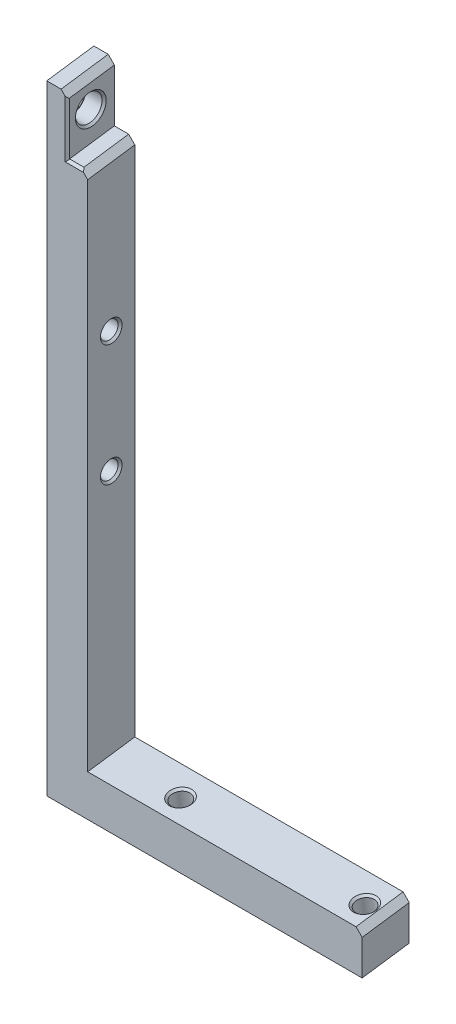
SolidWorks part; units mm, degrees
ref_plane "Top" through (0, 0, 0) normal (0, 0, 1) x (1, 0, 0)
ref_plane "Front" through (0, 0, 0) normal (0, 1, 0) x (1, 0, 0)
ref_plane "Right" through (0, 0, 0) normal (1, 0, 0) x (0, 0, -1)
sketch "Sketch4" plane through (0, 0, 0) normal (1, 0, 0) x (0, 0, -1)
  line L1 (0, 0) -> (11.5, 0)
  line L2 (0, 0) -> (0, 144)
  line L3 (0, 144) -> (11.5, 144)
  line L4 (11.5, 0) -> (11.5, 144)
  dimension "D1" = 11.5
  dimension "D2" = 144
extrude "Boss-Extrude2" add sketch "Sketch4" along normal blind 10
sketch "Sketch6" plane through (10, 0, 0) normal (1, 0, 0) x (0, 0, -1)
  line L0 (5.75, 0) -> (11.5, 0.8081)
  line L1 (0, 0) -> (11.5, 0) construction
  line L2 (11.5, 0) -> (11.5, 144) construction
  line L3 (11.5, 0.8081) -> (10.1083, 10.7108)
  line L4 (10.1083, 10.7108) -> (0.2056, 9.3191)
  line L5 (0.2056, 9.3191) -> (1.5973, -0.5836)
  line L6 (1.5973, -0.5836) -> (5.75, 0)
  line L7 (0, 144) -> (0, 0) construction
  dimension "D1" = 10
  dimension "D2" = 10
  dimension "D3" = 82
extrude "Boss-Extrude3" add sketch "Sketch6" along normal blind 67 and the other way blind 10
sketch "Sketch7" plane through (10, 0, 0) normal (1, 0, 0) x (0, 0, -1)
  line L0 (-3.1126, -1.2456) -> (11.8209, -3.029)
  line L2 (11.8209, -3.029) -> (11.8209, 0.8532)
  line L3 (11.8209, 0.8532) -> (-3.1126, -1.2456)
  line L4 (1.5973, -0.5836) -> (11.5, 0.8081) construction
extrude "Cut-Extrude2" cut sketch "Sketch7" against normal blind 10
sketch "Sketch8" plane through (0, 9.1102, 1.2804) normal (0, 0.9903, 0.1392) x (1, 0, 0)
  line L0 (10, 1.5005) -> (77, 1.5005) construction
  line L1 (77, 11.5005) -> (77, 1.5005) construction
  circle A0 centre (72.5, 6.5005) radius 2.25
  circle A1 centre (27.5, 6.5005) radius 2.25
  dimension "D2" = 4.5
  dimension "D3" = 4.5
  dimension "D1" = 45
  dimension "D4" = 5
  dimension "D5" = 4.5
extrude "Cut-Extrude3" cut sketch "Sketch8" against normal blind 10
sketch "Sketch11" plane through (0, 9.1102, 1.2804) normal (0, 0.9903, 0.1392) x (1, 0, 0)
  line L0 (23.5, 6.5005) -> (23.5, 0)
  line L1 (23.5, 0) -> (31.5, 0)
  line L3 (31.5, 0) -> (31.5, 6.5005)
  line L4 (10, 0) -> (0, 0) construction
  circle A0 centre (27.5, 6.5005) radius 4 construction
  arc A1 (31.5, 6.5005) -> (23.5, 6.5005) centre (27.5, 6.5005) ccw
  dimension "D1" = 8
sketch "Sketch12" plane through (77, 0, 0) normal (1, 0, 0) x (0, 0, -1)
  line L5 (0.2056, 9.3191) -> (10.1083, 10.7108) construction
  line L13 (1.5973, -0.5836) -> (0, -0.8081)
  line L14 (0, -0.8081) -> (0, 9.2902)
  line L16 (1.5973, -0.5836) -> (11.5, 0.8081) construction
  line L17 (0, 144) -> (0, 0) construction
  line L18 (11.5, 0.8081) -> (11.5, 10.9064)
  line L20 (11.5, 10.9064) -> (10.1083, 10.7108)
  line L21 (10.1083, 10.7108) -> (11.5, 0.8081)
  line L22 (10.1083, 10.7108) -> (0.2056, 9.3191) construction
  line L23 (11.5, 0.8081) -> (11.5, 144) construction
  line L25 (11.5, 0.8081) -> (10.1083, 10.7108) construction
  line L26 (0, 9.2902) -> (0.2056, 9.3191)
  line L27 (0.2056, 9.3191) -> (1.5973, -0.5836)
  line L28 (0.2056, 9.3191) -> (1.5973, -0.5836) construction
extrude "Boss-Extrude4" add sketch "Sketch12" against normal up to surface (77 mm away) up to face at (0, 48.0374, -4.3521)
sketch "Sketch13" plane through (10, 0, 0) normal (1, 0, 0) x (0, 0, -1)
  line L0 (11.5, 144) -> (11.5, 152)
  line L1 (11.5, 152) -> (0, 150.3838)
  line L2 (0, 150.3838) -> (0, 144)
  line L3 (0, 144) -> (11.5, 144)
  line L4 (11.5, 10.9064) -> (0, 9.2902) construction
  dimension "D1" = 8
extrude "Boss-Extrude5" add sketch "Sketch13" against normal blind 10
sketch "Sketch14" plane through (10, 0, 0) normal (1, 0, 0) x (0, 0, -1)
  line L0 (11.5, 10.9064) -> (11.5, 152) construction
  circle A0 centre (5.75, 144) radius 3.25
  dimension "D2" = 6.5
  dimension "D1" = 8
  dimension "D3" = 5.75
extrude "Cut-Extrude5" cut sketch "Sketch14" against normal blind 10
sketch "Sketch18" plane through (10, 0, 0) normal (1, 0, 0) x (0, 0, -1)
  line L0 (5.75, 99.6) -> (5.75, 70)
  line L1 (11.5, 10.9064) -> (11.5, 152) construction
  dimension "D1" = 5.75
  dimension "D2" = 29.6
  dimension "D3" = 70
hole_wizard "M4 Clearance Hole1" positions "Sketch19" profile "Sketch20" hole size "M4" standard "DIN" end condition through all
sketch "Sketch19" plane through (10, 0, 0) normal (1, 0, 0) x (0, 0, -1)
  point P0 (5.75, 70)
  point P3 (5.75, 99.6)
sketch "Sketch20" plane through (10, 70, -5.75) normal (0, 1, 0) x (0, 0, -1)
  line L0 (0, 0) -> (0, 10)
  line L1 (0, 10) -> (2.15, 10)
  line L2 (2.15, 10) -> (2.15, 0)
  line L5 (2.15, 0) -> (0, 0)
  line L11 (0, -6.35) -> (0, 107.95) construction
  dimension "Thru Hole Dia." = 4.3
  dimension "Thru Hole Depth" = 10
sketch "Sketch24" plane through (10, 0, 0) normal (1, 0, 0) x (0, 0, -1)
  line L0 (11.5, 152) -> (0, 150.3838)
  line L1 (0, 150.3838) -> (0, 136)
  line L2 (0, 150.3838) -> (0, 9.2902) construction
  line L3 (0, 136) -> (11.5, 137.6162)
  line L4 (11.5, 10.9064) -> (11.5, 152) construction
  line L5 (11.5, 137.6162) -> (11.5, 152)
  circle A0 centre (5.75, 144) radius 3.25 construction
  dimension "D1" = 8
extrude "Cut-Extrude7" cut sketch "Sketch24" against normal blind 5
chamfer "Chamfer2" distance 0.5 angle 45 10 edges at (10, 70, -7.9) (0, 70, -7.9) (10, 99.6, -7.9) (0, 99.6, -7.9) (0, 144, -9) (27.5, 9.7018, -2.9288) (27.5, -0.2009, -4.3206) (72.5, 9.7018, -2.9288) (72.5, -0.2009, -4.3206) (5, 144, -9)
chamfer "Chamfer5" distance 0.5 angle 45 2 edges at (7.5, 136, 0) (5, 143.1919, 0) first distance on face at (23, 73.7165, 0)
chamfer "Chamfer6" distance 1.5 angle 45 2 edges at (5, 151.227, -6) (10, 136.849, -6.0409)
chamfer "Chamfer7" distance 1.5 angle 45 1 edges at (77, 10.0983, -5.75)
